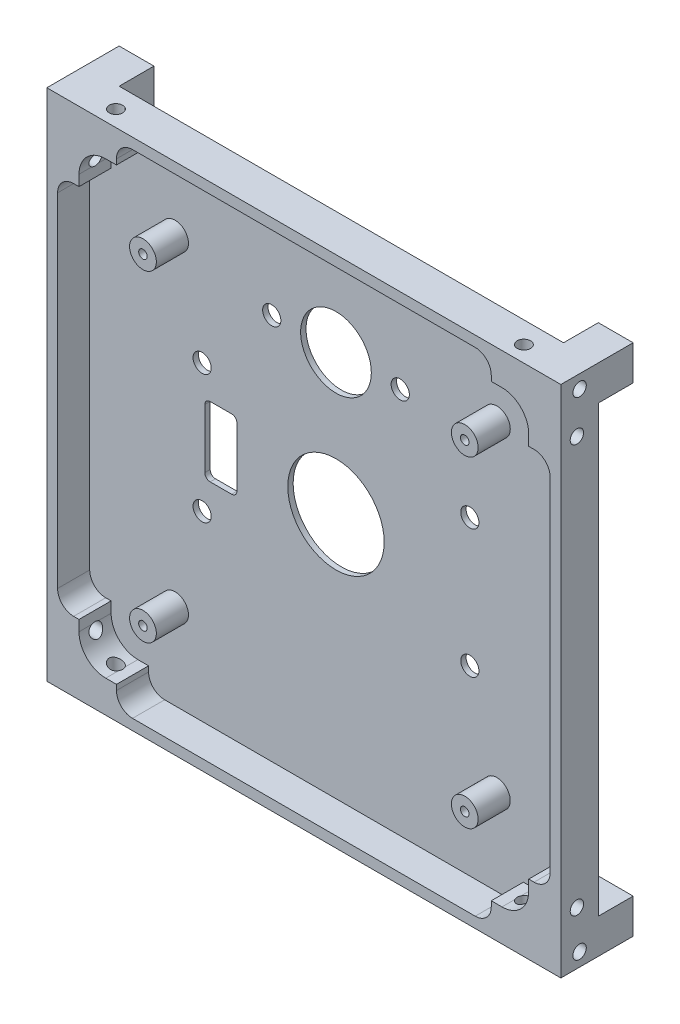
SolidWorks part; units mm, degrees
material "7075-T6 (SN)"
ref_plane "Front Plane" through (0, 0, 0) normal (0, 0, 1) x (1, 0, 0)
ref_plane "Top Plane" through (0, 0, 0) normal (0, 1, 0) x (1, 0, 0)
ref_plane "Right Plane" through (0, 0, 0) normal (1, 0, 0) x (0, 0, -1)
sketch "Sketch1" plane through (0, 0, 0) normal (0, 0, 1) x (1, 0, 0)
  line L1 (48, -48) -> (-48, -48)
  line L2 (48, -48) -> (48, 48)
  line L3 (48, 48) -> (-48, 48)
  line L4 (-48, -48) -> (-48, 48)
  line L5 (48, -48) -> (-48, 48) construction
  line L6 (48, 48) -> (-48, -48) construction
  point P0 (0, 0)
  dimension "D1" = 96
  dimension "D2" = 96
extrude "Boss-Extrude1" add sketch "Sketch1" along normal blind 2
sketch "Sketch2" plane through (0, 0, 2) normal (0, 0, 1) x (1, 0, 0)
  line L0 (48, 48) -> (-48, 48) construction
  line L1 (37, -42) -> (-37, -42)
  line L2 (42, -37) -> (42, 37)
  line L3 (37, 42) -> (-37, 42)
  line L4 (-42, -37) -> (-42, 37)
  line L5 (42, -42) -> (-42, 42) construction
  line L6 (42, 42) -> (-42, -42) construction
  line L7 (48, -48) -> (48, 48) construction
  line L12 (-48, 48) -> (-48, -48)
  line L13 (-48, -48) -> (48, -48)
  line L14 (48, -48) -> (48, 48)
  line L15 (48, 48) -> (-48, 48)
  line L16 (-48, 48) -> (-48, -48)
  line L17 (-48, -48) -> (48, -48)
  line L18 (48, -48) -> (48, 48)
  line L19 (48, 48) -> (-48, 48)
  arc A0 (-37, -42) -> (-42, -37) centre (-37, -37) cw
  arc A1 (37, -42) -> (42, -37) centre (37, -37) ccw
  arc A2 (42, 37) -> (37, 42) centre (37, 37) ccw
  arc A3 (-37, 42) -> (-42, 37) centre (-37, 37) ccw
  point P0 (0, 0)
  dimension "D4" = 5
  dimension "D1" = 6
  dimension "D2" = 6
extrude "Boss-Extrude2" add sketch "Sketch2" along normal blind 5
sketch "Sketch4" plane through (0, 0, 7) normal (0, 0, 1) x (1, 0, 0)
  line L0 (-41.5, 41.5) -> (41.5, -41.5) construction
  line L1 (-41.5, 41.5) -> (41.5, 41.5)
  line L2 (-41.5, 41.5) -> (-41.5, -41.5)
  line L3 (-41.5, -41.5) -> (41.5, -41.5)
  line L4 (41.5, 41.5) -> (41.5, -41.5)
  point P4 (0, 0)
  dimension "D1" = 83
  dimension "D2" = 83
sketch "Sketch3" plane through (0, 0, 0) normal (0, 0, -1) x (-1, 0, 0)
  line L1 (-48, 48) -> (-41.5, 48)
  line L2 (-48, 48) -> (-48, 41.5)
  line L3 (-48, 41.5) -> (-41.5, 41.5)
  line L4 (-41.5, 48) -> (-41.5, 41.5)
  line L5 (48, 48) -> (41.5, 48)
  line L6 (48, 48) -> (48, 41.5)
  line L7 (48, 41.5) -> (41.5, 41.5)
  line L8 (41.5, 48) -> (41.5, 41.5)
  line L9 (-48, -48) -> (-41.5, -48)
  line L10 (-48, -48) -> (-48, -41.5)
  line L11 (-48, -41.5) -> (-41.5, -41.5)
  line L12 (-41.5, -48) -> (-41.5, -41.5)
  line L13 (48, -48) -> (41.5, -48)
  line L14 (48, -48) -> (48, -41.5)
  line L15 (48, -41.5) -> (41.5, -41.5)
  line L16 (41.5, -48) -> (41.5, -41.5)
  dimension "D1" = 6.5
  dimension "D2" = 6.5
  dimension "D3" = 6.5
  dimension "D4" = 6.5
extrude "Boss-Extrude3" add sketch "Sketch3" along normal blind 6.5
sketch "Sketch5" plane through (0, 0, 0) normal (0, 0, -1) x (-1, 0, 0)
  circle A0 centre (0, 0) radius 9
  dimension "D1" = 18
extrude "Cut-Extrude1" cut sketch "Sketch5" against normal blind 10
sketch "Sketch6" plane through (-48, 0, 0) normal (-1, 0, 0) x (0, 0, 1)
  line L0 (-6.5, -45.5) -> (7, -45.5) construction
  line L2 (7, 48) -> (7, -48) construction
  line L3 (-6.5, 45.5) -> (7, 45.5) construction
  line L5 (7, 48) -> (-6.5, 48) construction
  line L6 (7, -48) -> (-6.5, -48) construction
  point P6 (3.5, -45.5)
  point P11 (3.5, 45.5)
  dimension "D1" = 3.5
  dimension "D2" = 3.5
  dimension "D3" = 2.5
  dimension "D4" = 2.5
hole_wizard "M3 Tapped Hole1" positions "3DSketch1" profile "Sketch7" tap size "M3" standard "ISO"
sketch3d "3DSketch1"
  point P0 (-48, 45.5, 3.5)
  point P3 (-48, -45.5, 3.5)
sketch "Sketch7" plane through (-48, 45.5, 3.5) normal (0, 1, 0) x (0, 0, 1)
  line L0 (0, 0) -> (0, 7.4511)
  line L1 (0, 7.4511) -> (1.25, 6.7)
  line L2 (1.25, 6.7) -> (1.25, 0)
  line L5 (1.25, 0) -> (0, 0)
  line L10 (0, 7.4511) -> (-1.25, 6.7) construction
  line L11 (0, -6.35) -> (0, 107.95) construction
  dimension "Tap Drill Dia." = 2.5
  dimension "Tap Drill Depth" = 6.7
  dimension "Drill Angle" = 118
cosmetic thread "Hole Thread1" parameters "D1"=6, "D2"=3
cosmetic thread "Hole Thread2" parameters "D1"=6, "D2"=3
mirror "Mirror1" about plane through (0, 0, 0) normal (1, 0, 0) of "M3 Tapped Hole1"
sketch "Sketch8" plane through (48, 0, 0) normal (1, 0, 0) x (0, 0, -1)
  point P0 (-4, -38.0996)
  point P1 (-4, 38.1004)
hole_wizard "M3 Tapped Hole2" positions "3DSketch2" profile "Sketch10" tap size "M3" standard "ISO"
sketch3d "3DSketch2"
  point P0 (48, 38.1004, 4)
  point P3 (48, -38.0996, 4)
sketch "Sketch10" plane through (48, 38.1004, 4) normal (0, 1, 0) x (0, 0, -1)
  line L0 (0, 0) -> (0, 9.2511)
  line L1 (0, 9.2511) -> (1.25, 8.5)
  line L2 (1.25, 8.5) -> (1.25, 0)
  line L5 (1.25, 0) -> (0, 0)
  line L10 (0, 9.2511) -> (-1.25, 8.5) construction
  line L11 (0, -6.35) -> (0, 107.95) construction
  dimension "Tap Drill Dia." = 2.5
  dimension "Tap Drill Depth" = 8.5
  dimension "Drill Angle" = 118
cosmetic thread "Hole Thread3" parameters "D1"=6, "D2"=3
cosmetic thread "Hole Thread4" parameters "D1"=6, "D2"=3
ref_axis "Axis1" through (0, 0, 2) along (0, 0, -1)
pattern_circular "CirPattern1" count 4 every 90 about axis through (0, 0, 2) along (0, 0, -1) of "M3 Tapped Hole2"
sketch "Sketch11" plane through (0, 0, 7) normal (0, 0, 1) x (1, 0, 0)
  line L0 (-37, -42) -> (37, -42) construction
  line L1 (32, -46) -> (-32, -46)
  line L2 (35, -43) -> (35, -42)
  line L3 (35, -42) -> (-35, -42)
  line L4 (-35, -43) -> (-35, -42)
  line L5 (-48, -48) -> (48, -48) construction
  line L6 (48, -48) -> (48, 48) construction
  line L7 (-48, 48) -> (-48, -48) construction
  line L8 (48, 48) -> (-48, 48) construction
  line L9 (-42, -35) -> (-43, -35)
  line L10 (-42, -35) -> (-42, 35)
  line L11 (-42, 35) -> (-43, 35)
  line L12 (-37, -42) -> (37, -42)
  line L13 (42, -37) -> (42, 37)
  line L14 (37, 42) -> (-37, 42)
  line L15 (-42, 37) -> (-42, -37)
  line L16 (-37, -42) -> (37, -42)
  line L17 (42, -37) -> (42, 37)
  line L18 (37, 42) -> (-37, 42)
  line L19 (-42, 37) -> (-42, -37)
  line L20 (-46, -32) -> (-46, 32)
  arc A0 (-43, 35) -> (-46, 32) centre (-43, 32) ccw
  arc A1 (-43, -35) -> (-46, -32) centre (-43, -32) cw
  arc A2 (-32, -46) -> (-35, -43) centre (-32, -43) cw
  arc A3 (32, -46) -> (35, -43) centre (32, -43) ccw
  arc A4 (-42, -37) -> (-37, -42) centre (-37, -37) ccw
  arc A5 (37, -42) -> (42, -37) centre (37, -37) ccw
  arc A6 (42, 37) -> (37, 42) centre (37, 37) ccw
  arc A7 (-37, 42) -> (-42, 37) centre (-37, 37) ccw
  arc A8 (-42, -37) -> (-37, -42) centre (-37, -37) ccw
  arc A9 (37, -42) -> (42, -37) centre (37, -37) ccw
  arc A10 (42, 37) -> (37, 42) centre (37, 37) ccw
  arc A11 (-37, 42) -> (-42, 37) centre (-37, 37) ccw
  point P10 (-35, -42.5)
  line M21 (37, -42) -> (-37, -42)
  line M23 (-42, -37) -> (-42, 37)
  dimension "D1" = 2
  dimension "D8" = 3
  dimension "D2" = 13
  dimension "D3" = 13
  dimension "D5" = 13
  dimension "D6" = 13
  dimension "D7" = 2
extrude "Cut-Extrude2" cut sketch "Sketch11" against normal up to surface (5 mm away) contours A1 L9 L11 A0 L20 M23 | L1 A3 L2 L4 A2 M21 region at (0, -43.9814, 7) region at (-43.9814, 0, 7) up to face at (9, 0, 2)
pattern_circular "CirPattern2" count 2 every 180 about axis through (0, 0, 2) along (0, 0, -1) of "Cut-Extrude2"
sketch "Sketch12" plane through (0, 0, 2) normal (0, 0, 1) x (1, 0, 0)
  line L20 (-37, -42) -> (-35, -42)
  line L21 (-35, -42) -> (-35, -43)
  line L22 (-32, -46) -> (32, -46)
  line L23 (35, -43) -> (35, -42)
  line L24 (35, -42) -> (37, -42)
  line L25 (42, -37) -> (42, -35)
  line L26 (42, -35) -> (43, -35)
  line L27 (46, -32) -> (46, 32)
  line L28 (43, 35) -> (42, 35)
  line L29 (42, 35) -> (42, 37)
  line L30 (37, 42) -> (35, 42)
  line L31 (35, 42) -> (35, 43)
  line L32 (32, 46) -> (-32, 46)
  line L33 (-35, 43) -> (-35, 42)
  line L34 (-35, 42) -> (-37, 42)
  line L35 (-42, 37) -> (-42, 35)
  line L36 (-42, 35) -> (-43, 35)
  line L37 (-46, 32) -> (-46, -32)
  line L38 (-43, -35) -> (-42, -35)
  line L39 (-42, -35) -> (-42, -37)
  line L40 (-37, -42) -> (-35, -42)
  line L41 (-35, -42) -> (-35, -43)
  line L42 (-32, -46) -> (32, -46)
  line L43 (35, -43) -> (35, -42)
  line L44 (35, -42) -> (37, -42)
  line L45 (42, -37) -> (42, -35)
  line L46 (42, -35) -> (43, -35)
  line L47 (46, -32) -> (46, 32)
  line L48 (43, 35) -> (42, 35)
  line L49 (42, 35) -> (42, 37)
  line L50 (37, 42) -> (35, 42)
  line L51 (35, 42) -> (35, 43)
  line L52 (32, 46) -> (-32, 46)
  line L53 (-35, 43) -> (-35, 42)
  line L54 (-35, 42) -> (-37, 42)
  line L55 (-42, 37) -> (-42, 35)
  line L56 (-42, 35) -> (-43, 35)
  line L57 (-46, 32) -> (-46, -32)
  line L58 (-43, -35) -> (-42, -35)
  line L59 (-42, -35) -> (-42, -37)
  arc A12 (-42, -37) -> (-37, -42) centre (-37, -37) ccw
  arc A13 (-35, -43) -> (-32, -46) centre (-32, -43) ccw
  arc A14 (32, -46) -> (35, -43) centre (32, -43) ccw
  arc A15 (37, -42) -> (42, -37) centre (37, -37) ccw
  arc A16 (43, -35) -> (46, -32) centre (43, -32) ccw
  arc A17 (46, 32) -> (43, 35) centre (43, 32) ccw
  arc A18 (42, 37) -> (37, 42) centre (37, 37) ccw
  arc A19 (35, 43) -> (32, 46) centre (32, 43) ccw
  arc A20 (-32, 46) -> (-35, 43) centre (-32, 43) ccw
  arc A21 (-37, 42) -> (-42, 37) centre (-37, 37) ccw
  arc A22 (-43, 35) -> (-46, 32) centre (-43, 32) ccw
  arc A23 (-46, -32) -> (-43, -35) centre (-43, -32) ccw
  arc A24 (-42, -37) -> (-37, -42) centre (-37, -37) ccw
  arc A25 (-35, -43) -> (-32, -46) centre (-32, -43) ccw
  arc A26 (32, -46) -> (35, -43) centre (32, -43) ccw
  arc A27 (37, -42) -> (42, -37) centre (37, -37) ccw
  arc A28 (43, -35) -> (46, -32) centre (43, -32) ccw
  arc A29 (46, 32) -> (43, 35) centre (43, 32) ccw
  arc A30 (42, 37) -> (37, 42) centre (37, 37) ccw
  arc A31 (35, 43) -> (32, 46) centre (32, 43) ccw
  arc A32 (-32, 46) -> (-35, 43) centre (-32, 43) ccw
  arc A33 (-37, 42) -> (-42, 37) centre (-37, 37) ccw
  arc A34 (-43, 35) -> (-46, 32) centre (-43, 32) ccw
  arc A35 (-46, -32) -> (-43, -35) centre (-43, -32) ccw
  dimension "D1" = 0
extrude "Cut-Extrude3" cut sketch "Sketch12" against normal blind 1
sketch "Sketch13" plane through (0, 0, 7) normal (0, 0, 1) x (1, 0, 0)
  line L4 (48, 48) -> (-48, 48)
  line L5 (-48, 48) -> (-48, -48)
  line L6 (-48, -48) -> (48, -48)
  line L7 (48, -48) -> (48, 48)
  line L8 (48, 48) -> (-48, 48)
  line L9 (-48, 48) -> (-48, -48)
  line L10 (-48, -48) -> (48, -48)
  line L11 (48, -48) -> (48, 48)
  dimension "D1" = 0
extrude "Cut-Extrude4" [suppressed] cut sketch "Sketch13" against normal blind 1
sketch "Sketch14" plane through (0, 0, 0) normal (0, 0, -1) x (-1, 0, 0)
  circle A0 centre (0, 0) radius 20
  text T0 "MSSG       -      EYE-SAT" font "Impact" height 4
  dimension "D1" = 40
sketch "Sketch15" plane through (0, 0, 1) normal (0, 0, 1) x (1, 0, 0)
  line L0 (0, 0) -> (-35.5279, 35.5279) construction
  line L1 (0, 0) -> (-32.9127, -32.9127) construction
  circle A0 centre (0, 0) radius 42.5 construction
  circle A1 centre (-30.052, 30.052) radius 2.5
  point P2 (30.052, 30.052)
  point P6 (30.052, -30.052)
  point P9 (-30.052, -30.052)
  point P10 (-30.052, 30.052)
extrude "Boss-Extrude4" add sketch "Sketch15" along normal blind 6
pattern_circular "CirPattern3" count 4 over 360 about axis through (0, 0, 2) along (0, 0, -1) of "Boss-Extrude4" reverse direction yes
hole_wizard "Tap Drill for M2x0.4 Tap1" positions "3DSketch3" profile "Sketch16" hole size "M2x0.4" standard "ANSI Metric"
sketch3d "3DSketch3"
  line L3 (-30.052, 30.052, 7) -> (-30.052, 30.052, 1) construction
  point P0 (-30.052, 30.052, 7)
  point P17 (-30.052, 30.052, 7)
sketch "Sketch16" plane through (-30.052, 30.052, 7) normal (1, 0, 0) x (0, -1, 0)
  line L0 (0, 0) -> (0, 6.4797)
  line L1 (0, 6.4797) -> (0.8, 5.999)
  line L2 (0.8, 5.999) -> (0.8, 0)
  line L5 (0.8, 0) -> (0, 0)
  line L10 (0, 6.4797) -> (-0.8, 5.999) construction
  line L11 (0, -6.35) -> (0, 107.95) construction
  dimension "Hole Dia." = 1.6
  dimension "Hole Depth" = 5.999
  dimension "Drill Angle" = 118
pattern_circular "CirPattern4" count 4 over 360 about axis through (0, 0, 2) along (0, 0, -1) of "Tap Drill for M2x0.4 Tap1"
sketch "Sketch17" plane through (0, 0, 1) normal (0, 0, 1) x (1, 0, 0)
  line L1 (-18.5, -6.5) -> (-24.5, -6.5)
  line L2 (-18.5, -6.5) -> (-18.5, 6.5)
  line L3 (-18.5, 6.5) -> (-24.5, 6.5)
  line L4 (-24.5, -6.5) -> (-24.5, 6.5)
  line L5 (-18.5, -6.5) -> (-24.5, 6.5) construction
  line L6 (-18.5, 6.5) -> (-24.5, -6.5) construction
  point P0 (-21.5, 0)
  dimension "D1" = 13
  dimension "D2" = 6
  dimension "D3" = 21.5
extrude "Cut-Extrude5" cut sketch "Sketch17" against normal blind 10
hole_wizard "M3 Clearance Hole1" positions "3DSketch4" profile "Sketch18" hole size "M3" standard "ANSI Metric" end condition through all
sketch3d "3DSketch4"
  point P0 (-25, -12, 1)
sketch "Sketch18" plane through (-25, -12, 1) normal (1, 0, 0) x (0, -1, 0)
  line L0 (0, 0) -> (0, 7.5)
  line L1 (0, 7.5) -> (1.7, 7.5)
  line L2 (1.7, 7.5) -> (1.7, 0)
  line L5 (1.7, 0) -> (0, 0)
  line L11 (0, -6.35) -> (0, 107.95) construction
  dimension "Thru Hole Dia." = 3.4
  dimension "Thru Hole Depth" = 7.5
hole_wizard "M3 Clearance Hole2" positions "Sketch22" profile "Sketch23" hole size "M3" standard "ISO"
sketch "Sketch22" plane through (0, 0, 1) normal (0, 0, 1) x (1, 0, 0)
  point P0 (-12, 26.2)
  point P2 (12, 26.2)
  dimension "D1" = 12
  dimension "D2" = 26.2
  dimension "D3" = 26.2
  dimension "D4" = 12
sketch "Sketch23" plane through (-12, 26.2, 1) normal (1, 0, 0) x (0, -1, 0)
  line L0 (0, 0) -> (0, 14.5515)
  line L1 (0, 14.5515) -> (1.7, 13.53)
  line L2 (1.7, 13.53) -> (1.7, 0)
  line L5 (1.7, 0) -> (0, 0)
  line L10 (0, 14.5515) -> (-1.7, 13.53) construction
  line L11 (0, -6.35) -> (0, 107.95) construction
  dimension "Hole Dia." = 3.4
  dimension "Hole Depth" = 13.53
  dimension "Drill Angle" = 118
sketch "Sketch24" plane through (0, 0, 1) normal (0, 0, 1) x (1, 0, 0)
  circle A0 centre (0, 26.2) radius 6.6
extrude "Cut-Extrude6" cut sketch "Sketch24" against normal blind 10
mirror "Mirror2" about plane through (0, 0, 0) normal (0, 1, 0) of "M3 Clearance Hole1"
mirror "Mirror3" about plane through (0, 0, 0) normal (1, 0, 0) of "M3 Clearance Hole1"
pattern_circular "CirPattern5" count 2 over 360 about axis through (0, 0, 2) along (0, 0, -1) of "M3 Clearance Hole1"
fillet "Fillet1" radius 1 4 edges at (-24.5, -6.5, 0.5) (-24.5, 6.5, 0.5) (-18.5, -6.5, 0.5) (-18.5, 6.5, 0.5)
equation "\"D2@Sketch1\"=\"D1@Sketch1\""
equation "\"thickness\" = 2"
equation "\"D1@Boss-Extrude1\"=\"thickness\""
equation "\"D2@Sketch2\"=\"D1@Sketch2\""
equation "\"D2@Sketch3\"=\"D1@Sketch3\""
equation "\"D3@Sketch3\"=\"D1@Sketch3\""
equation "\"D4@Sketch3\"=\"D1@Sketch3\""
equation "\"D2@Sketch4\"=\"D1@Sketch4\""
equation "\"D2@Sketch6\"=\"D1@Sketch6\""
equation "\"D4@Sketch6\"=\"D3@Sketch6\""
equation "\"D3@Sketch11\"=\"D2@Sketch11\""
equation "\"D5@Sketch11\"=\"D2@Sketch11\""
equation "\"D6@Sketch11\"=\"D2@Sketch11\""
equation "\"D7@Sketch11\"=\"D1@Sketch11\""
